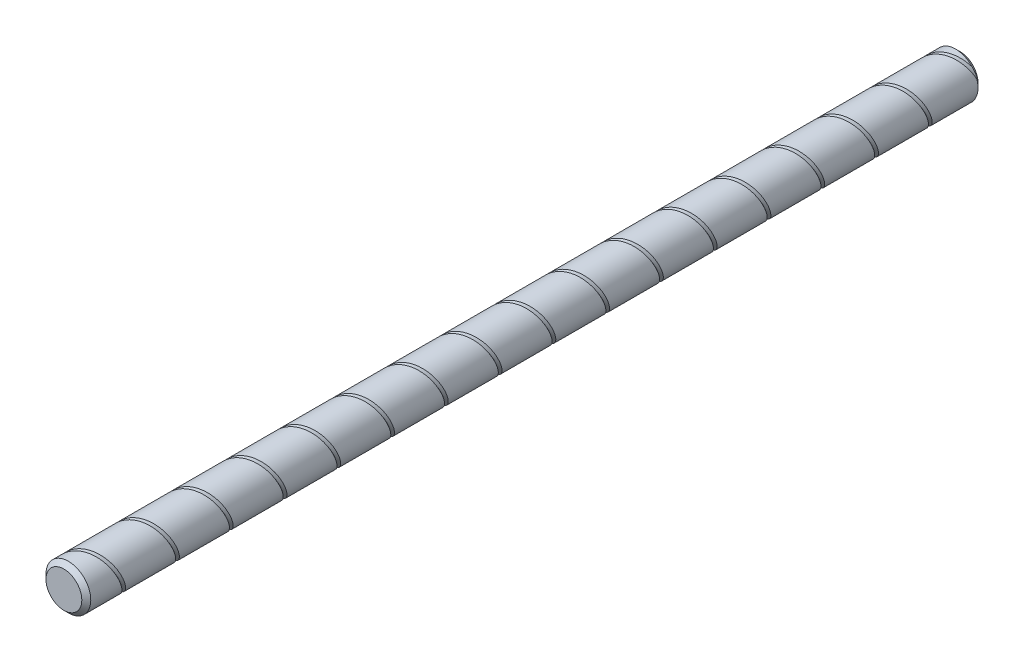
SolidWorks part; units mm, degrees
ref_plane "Front" through (0, 0, 0) normal (0, 0, 1) x (1, 0, 0)
ref_plane "Top" through (0, 0, 0) normal (0, 1, 0) x (1, 0, 0)
ref_plane "Right" through (0, 0, 0) normal (1, 0, 0) x (0, 0, -1)
sketch "Sketch1" plane through (0, 0, 0) normal (0, 1, 0) x (1, 0, 0)
  line L0 (0, 0) -> (0, 200)
  line L1 (0, 200) -> (4, 200)
  line L2 (5, 199) -> (5, 1)
  line L3 (4, 0) -> (0, 0)
  line L4 (0, 0) -> (0.0888, -0.2719)
  line L5 (4, 200) -> (5, 199)
  line L6 (5, 1) -> (4, 0)
  point P5 (5, 200)
  point P6 (5, 0)
  dimension "D1" = 5
  dimension "D2" = 200
revolve "Revolve1" add sketch "Sketch1" angle 360 about L0 region at (2.4978, 0, -100)
sketch "Sketch2" plane through (0, 0, -200) normal (0, 0, -1) x (-1, 0, 0)
  circle A0 centre (0, 0) radius 5 construction
  circle A1 centre (0, 0) radius 5
curve "Helix/Spiral1" pitch 12 height 360 radius 5 centre (0, 0, -200) axis (0, 0, 1) start towards (-1, 0, 0)
ref_plane "Plane1" through (5, 0, -200) normal (0, 0.9342, 0.3568) x (1, 0, 0)
sketch "Sketch3" plane through (5, 0, -200) normal (0, 0.9342, 0.3568) x (1, 0, 0)
  line L1 (0.3333, -0.5774) -> (0.3333, 0.5774)
  line L2 (0.3333, 0.5774) -> (-0.6667, 0)
  line L3 (-0.6667, 0) -> (0.3333, -0.5774)
  circle A0 centre (0, 0) radius 0.3333 construction
  dimension "D1" = 1
sweep "Cut-Sweep1" cut profiles "Sketch3" path "Helix/Spiral1" align with end faces yes
